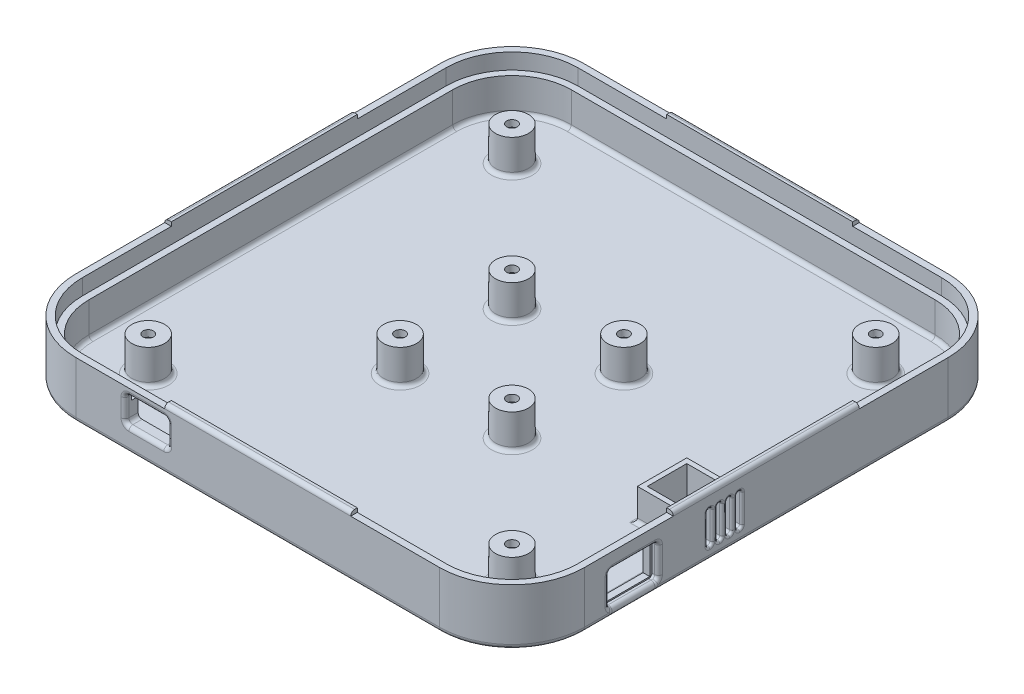
SolidWorks part; units mm, degrees
ref_plane "Front Plane" through (0, 0, 0) normal (0, 0, 1) x (1, 0, 0)
ref_plane "Top Plane" through (0, 0, 0) normal (0, 1, 0) x (1, 0, 0)
ref_plane "Right Plane" through (0, 0, 0) normal (1, 0, 0) x (0, 0, -1)
sketch "Sketch1" plane through (0, 0, 0) normal (0, 1, 0) x (1, 0, 0)
  line L0 (0, 75.25) -> (55.25, 75.25)
  line L1 (75.25, 55.25) -> (75.25, 0)
  line L2 (75.25, 0) -> (75.25, -55.25)
  line L3 (55.25, -75.25) -> (0, -75.25)
  line L4 (0, -75.25) -> (-55.25, -75.25)
  line L5 (-75.25, -55.25) -> (-75.25, 0)
  line L6 (-75.25, 0) -> (-75.25, 55.25)
  line L7 (-55.25, 75.25) -> (0, 75.25)
  line L8 (-55.25, 77.25) -> (0, 77.25)
  line L9 (0, 77.25) -> (55.25, 77.25)
  line L10 (77.25, 55.25) -> (77.25, 0)
  line L11 (77.25, 0) -> (77.25, -55.25)
  line L12 (55.25, -77.25) -> (0, -77.25)
  line L13 (0, -77.25) -> (-55.25, -77.25)
  line L14 (-77.25, -55.25) -> (-77.25, 0)
  line L15 (-77.25, 0) -> (-77.25, 55.25)
  arc A0 (55.25, 75.25) -> (75.25, 55.25) centre (55.25, 55.25) cw
  arc A1 (75.25, -55.25) -> (55.25, -75.25) centre (55.25, -55.25) cw
  arc A2 (-55.25, -75.25) -> (-75.25, -55.25) centre (-55.25, -55.25) cw
  arc A3 (-75.25, 55.25) -> (-55.25, 75.25) centre (-55.25, 55.25) cw
  arc A4 (55.25, 77.25) -> (77.25, 55.25) centre (55.25, 55.25) cw
  arc A5 (77.25, -55.25) -> (55.25, -77.25) centre (55.25, -55.25) cw
  arc A6 (-55.25, -77.25) -> (-77.25, -55.25) centre (-55.25, -55.25) cw
  arc A7 (-77.25, 55.25) -> (-55.25, 77.25) centre (-55.25, 55.25) cw
  point P24 (0, 0)
  dimension "D1" = 75.25
  dimension "D2" = 75.25
  dimension "D3" = 20
  dimension "D5" = 2
  dimension "D4" = 4
extrude "Boss-Extrude2" add sketch "Sketch1" along normal blind 15.2
sketch "Sketch4" plane through (0, 0, 0) normal (0, 1, 0) x (1, 0, 0)
  line L20 (55.25, 73.25) -> (-55.25, 73.25)
  line L21 (73.25, -55.25) -> (73.25, 55.25)
  line L22 (-55.25, -73.25) -> (55.25, -73.25)
  line L23 (-73.25, 55.25) -> (-73.25, -55.25)
  line L24 (55.25, 73.25) -> (-55.25, 73.25)
  line L25 (73.25, -55.25) -> (73.25, 55.25)
  line L26 (-55.25, -73.25) -> (55.25, -73.25)
  line L27 (-73.25, 55.25) -> (-73.25, -55.25)
  line L44 (55.25, 75.25) -> (-55.25, 75.25)
  line L45 (75.25, -55.25) -> (75.25, 55.25)
  line L46 (-55.25, -75.25) -> (55.25, -75.25)
  line L47 (-75.25, 55.25) -> (-75.25, -55.25)
  line L48 (55.25, 75.25) -> (-55.25, 75.25)
  line L49 (75.25, -55.25) -> (75.25, 55.25)
  line L50 (-55.25, -75.25) -> (55.25, -75.25)
  line L51 (-75.25, 55.25) -> (-75.25, -55.25)
  arc A24 (73.25, 55.25) -> (55.25, 73.25) centre (55.25, 55.25) ccw
  arc A25 (55.25, -73.25) -> (73.25, -55.25) centre (55.25, -55.25) ccw
  arc A26 (-73.25, -55.25) -> (-55.25, -73.25) centre (-55.25, -55.25) ccw
  arc A27 (-55.25, 73.25) -> (-73.25, 55.25) centre (-55.25, 55.25) ccw
  arc A28 (73.25, 55.25) -> (55.25, 73.25) centre (55.25, 55.25) ccw
  arc A29 (55.25, -73.25) -> (73.25, -55.25) centre (55.25, -55.25) ccw
  arc A30 (-73.25, -55.25) -> (-55.25, -73.25) centre (-55.25, -55.25) ccw
  arc A31 (-55.25, 73.25) -> (-73.25, 55.25) centre (-55.25, 55.25) ccw
  arc A52 (75.25, 55.25) -> (55.25, 75.25) centre (55.25, 55.25) ccw
  arc A53 (55.25, -75.25) -> (75.25, -55.25) centre (55.25, -55.25) ccw
  arc A54 (-75.25, -55.25) -> (-55.25, -75.25) centre (-55.25, -55.25) ccw
  arc A55 (-55.25, 75.25) -> (-75.25, 55.25) centre (-55.25, 55.25) ccw
  arc A56 (75.25, 55.25) -> (55.25, 75.25) centre (55.25, 55.25) ccw
  arc A57 (55.25, -75.25) -> (75.25, -55.25) centre (55.25, -55.25) ccw
  arc A58 (-75.25, -55.25) -> (-55.25, -75.25) centre (-55.25, -55.25) ccw
  arc A59 (-55.25, 75.25) -> (-75.25, 55.25) centre (-55.25, 55.25) ccw
  dimension "D1" = 2
  dimension "D2" = 0
extrude "Boss-Extrude3" add sketch "Sketch4" along normal blind 10.4
sketch "Sketch5" plane through (0, 0, 0) normal (0, -1, 0) x (1, 0, 0)
  line L8 (-55.25, -77.25) -> (55.25, -77.25)
  line L9 (77.25, -55.25) -> (77.25, 55.25)
  line L10 (55.25, 77.25) -> (-55.25, 77.25)
  line L11 (-77.25, 55.25) -> (-77.25, -55.25)
  line L12 (-55.25, -77.25) -> (55.25, -77.25)
  line L13 (77.25, -55.25) -> (77.25, 55.25)
  line L14 (55.25, 77.25) -> (-55.25, 77.25)
  line L15 (-77.25, 55.25) -> (-77.25, -55.25)
  arc A8 (-77.25, -55.25) -> (-55.25, -77.25) centre (-55.25, -55.25) ccw
  arc A9 (55.25, -77.25) -> (77.25, -55.25) centre (55.25, -55.25) ccw
  arc A10 (77.25, 55.25) -> (55.25, 77.25) centre (55.25, 55.25) ccw
  arc A11 (-55.25, 77.25) -> (-77.25, 55.25) centre (-55.25, 55.25) ccw
  arc A12 (-77.25, -55.25) -> (-55.25, -77.25) centre (-55.25, -55.25) ccw
  arc A13 (55.25, -77.25) -> (77.25, -55.25) centre (55.25, -55.25) ccw
  arc A14 (77.25, 55.25) -> (55.25, 77.25) centre (55.25, 55.25) ccw
  arc A15 (-55.25, 77.25) -> (-77.25, 55.25) centre (-55.25, 55.25) ccw
  dimension "D1" = 0
extrude "Boss-Extrude4" add sketch "Sketch5" along normal blind 2
sketch "Sketch6" plane through (0, 0, 77.25) normal (0, 0, 1) x (1, 0, 0)
  line L0 (-77.25, 15.2) -> (-77.25, -2) construction
  line L1 (-40.325, 5) -> (-27.325, 5)
  line L2 (-40.325, 5) -> (-40.325, 13)
  line L3 (-40.325, 13) -> (-27.325, 13)
  line L4 (-27.325, 5) -> (-27.325, 13)
  line L5 (-40.325, 5) -> (-27.325, 13) construction
  line L6 (-40.325, 13) -> (-27.325, 5) construction
  line L7 (55.25, -2) -> (-55.25, -2) construction
  point P0 (-33.825, 9)
  dimension "D1" = 13
  dimension "D2" = 43.425
  dimension "D3" = 11
  dimension "D4" = 8
extrude "Cut-Extrude1" cut sketch "Sketch6" against normal up to next
sketch "Sketch7" plane through (77.25, 0, 0) normal (1, 0, 0) x (0, 0, -1)
  line L0 (-13.4, 11.6) -> (-13.4, 1.6)
  line L1 (-17.9, 11.6) -> (-16.4, 11.6)
  line L2 (-17.9, 11.6) -> (-17.9, 1.6)
  line L3 (-17.9, 1.6) -> (-16.4, 1.6)
  line L4 (-16.4, 11.6) -> (-16.4, 1.6)
  line L5 (-14.9, 11.6) -> (-13.4, 11.6)
  line L6 (-14.9, 11.6) -> (-14.9, 1.6)
  line L7 (-14.9, 1.6) -> (-13.4, 1.6)
  line L8 (-10.4, 11.6) -> (-10.4, 1.6)
  line L9 (-11.9, 11.6) -> (-10.4, 11.6)
  line L10 (-11.9, 11.6) -> (-11.9, 1.6)
  line L11 (-11.9, 1.6) -> (-10.4, 1.6)
  line L12 (-7.4, 11.6) -> (-7.4, 1.6)
  line L13 (-8.9, 11.6) -> (-7.4, 11.6)
  line L14 (-8.9, 11.6) -> (-8.9, 1.6)
  line L15 (-8.9, 1.6) -> (-7.4, 1.6)
  line L16 (-13.4, 6.6) -> (-11.9, 6.6) construction
  line L17 (-14.9, 6.6) -> (-16.4, 6.6) construction
  line L18 (-10.4, 6.6) -> (-8.9, 6.6) construction
  line L19 (-77.25, 15.2) -> (-77.25, -2) construction
  line L21 (-55.25, 6.6) -> (55.25, 6.6) construction
  line L22 (-55.25, 15.2) -> (-55.25, -2) construction
  line L23 (55.25, 15.2) -> (55.25, -2) construction
  point P22 (-12.65, 6.6)
  dimension "D1" = 1.5
  dimension "D3" = 64.6
  dimension "D4" = 1.5
  dimension "D5" = 10
  dimension "D2" = 4
extrude "Cut-Extrude2" cut sketch "Sketch7" against normal up to next
fillet "Fillet4" radius 1.5 8 edges at (70.8063, -2, 70.8063) (77.25, -2, 0) (70.8063, -2, -70.8063) (0, -2, -77.25) (-70.8063, -2, -70.8063) (-77.25, -2, 0) (-70.8063, -2, 70.8063) (0, -2, 77.25)
sketch "Sketch10" plane through (0, 0, 0) normal (0, 1, 0) x (1, 0, 0)
  line L0 (73.25, -55.25) -> (73.25, 55.25) construction
  line L1 (73.25, -5.15) -> (58.25, -5.15)
  line L2 (73.25, -5.15) -> (73.25, -6.65)
  line L3 (73.25, -20.15) -> (58.25, -20.15)
  line L4 (58.25, -5.15) -> (58.25, -20.15)
  line L5 (-55.25, -77.25) -> (55.25, -77.25) construction
  line L6 (73.25, -18.65) -> (73.25, -20.15)
  line L7 (73.25, -6.65) -> (59.75, -6.65)
  line L9 (73.25, -18.65) -> (59.75, -18.65)
  line L10 (59.75, -6.65) -> (59.75, -18.65)
  point P7 (58.25, -12.65)
  dimension "D1" = 15
  dimension "D2" = 15
  dimension "D3" = 64.6
  dimension "D4" = 1.5
  dimension "D5" = 1.5
  dimension "D6" = 1.5
extrude "Boss-Extrude6" add sketch "Sketch10" along normal blind 9.5
sketch "Sketch14" plane through (0, -2, 0) normal (0, -1, 0) x (1, 0, 0)
  line L0 (-77.25, -55.25) -> (-77.25, 55.25) construction
  line L1 (-55.25, 77.25) -> (55.25, 77.25) construction
  line L2 (-75.75, 0) -> (75.75, 0) construction
  line L3 (-75.75, 55.25) -> (-75.75, -55.25) construction
  line L4 (75.75, -55.25) -> (75.75, 55.25) construction
  circle A0 centre (-55.25, 55.25) radius 3
  circle A1 centre (-17, 17) radius 3
  dimension "D1" = 6
  dimension "D4" = 6
  dimension "D2" = 22
  dimension "D3" = 22
  dimension "D5" = 17
  dimension "D6" = 17
extrude "Cut-Extrude5" cut sketch "Sketch14" against normal offset from surface (10.4 mm away) 2 up to face at (-12.4388, 10.4, -6.4731)
sketch "Sketch15" plane through (0, 0, 0) normal (0, 1, 0) x (1, 0, 0)
  circle A0 centre (-55.25, -55.25) radius 3
  circle A1 centre (-55.25, -55.25) radius 5
  circle A2 centre (-17, -17) radius 3
  circle A3 centre (-17, -17) radius 5
  dimension "D1" = 2
  dimension "D2" = 2
extrude "Boss-Extrude8" add sketch "Sketch15" along normal offset from surface (8.4 mm away) 2 up to face at (-12.4388, 10.4, -6.4731)
sketch "Sketch16" plane through (0, 8.4, 0) normal (0, 1, 0) x (1, 0, 0)
  circle A0 centre (-55.25, -55.25) radius 5
  circle A1 centre (-55.25, -55.25) radius 1.6
  circle A3 centre (-17, -17) radius 1.6
  circle A4 centre (-17, -17) radius 5
  dimension "D1" = 3.2
  dimension "D2" = 3.2
extrude "Boss-Extrude9" add sketch "Sketch16" along normal up to surface (2 mm away) up to face at (-12.4388, 10.4, -6.4731)
mirror "Mirror1" about plane through (0, 0, 0) normal (0, 0, 1) of "Boss-Extrude8", "Boss-Extrude9", "Cut-Extrude5"
mirror "Mirror2" about plane through (0, 0, 0) normal (1, 0, 0) of "Mirror1"
sketch "Sketch17" plane through (0, 15.2, 0) normal (0, 1, 0) x (1, 0, 0)
  line L0 (-55.25, -75.25) -> (55.25, -75.25) construction
  line L1 (-28.25, -75.25) -> (28.25, -75.25)
  line L2 (-28.25, -75.25) -> (-28.25, -77.25)
  line L3 (-28.25, -77.25) -> (28.25, -77.25)
  line L4 (28.25, -75.25) -> (28.25, -77.25)
  line L5 (-55.25, -77.25) -> (55.25, -77.25) construction
  line L6 (77.25, -55.25) -> (77.25, 55.25) construction
  line L7 (77.25, 28.25) -> (75.25, 28.25)
  line L8 (77.25, 28.25) -> (77.25, -28.25)
  line L9 (77.25, -28.25) -> (75.25, -28.25)
  line L10 (75.25, 28.25) -> (75.25, -28.25)
  line L11 (75.25, -55.25) -> (75.25, 55.25) construction
  line L12 (55.25, 77.25) -> (-55.25, 77.25) construction
  line L13 (28.25, 77.25) -> (-28.25, 77.25)
  line L14 (28.25, 77.25) -> (28.25, 75.25)
  line L15 (28.25, 75.25) -> (-28.25, 75.25)
  line L16 (-28.25, 77.25) -> (-28.25, 75.25)
  line L17 (55.25, 75.25) -> (-55.25, 75.25) construction
  line L18 (-75.25, 55.25) -> (-75.25, -55.25) construction
  line L19 (-75.25, 28.25) -> (-77.25, 28.25)
  line L20 (-75.25, 28.25) -> (-75.25, -28.25)
  line L21 (-75.25, -28.25) -> (-77.25, -28.25)
  line L22 (-77.25, 28.25) -> (-77.25, -28.25)
  line L23 (-77.25, 55.25) -> (-77.25, -55.25) construction
  dimension "D1" = 27
  dimension "D2" = 27
  dimension "D3" = 27
  dimension "D4" = 27
  dimension "D5" = 27
  dimension "D6" = 27
  dimension "D7" = 27
  dimension "D8" = 27
extrude "Boss-Extrude10" add sketch "Sketch17" along normal blind 1.2
fillet "Fillet7" radius 1.2 4 edges at (0, 16.4, 77.25) (77.25, 16.4, 0) (0, 16.4, -77.25) (-77.25, 16.4, 0)
fillet "Fillet8" radius 1.2 8 edges at (-40.325, 9, 77.25) (-33.825, 5, 77.25) (-33.825, 13, 77.25) (-27.325, 9, 77.25) (-27.325, 13, 76.25) (-40.325, 13, 76.25) (-40.325, 5, 75.25) (-27.325, 5, 75.25)
fillet "Fillet9" radius 0.75 40 edges at (75.25, 11, 7.4) (75.25, 11, 8.9) (75.25, 11, 10.4) (75.25, 11, 11.9) (75.25, 11, 13.4) (75.25, 11, 14.9) (75.25, 11, 16.4) (75.25, 11, 17.9) (73.25, 6, 8.9) (73.25, 6, 7.4) (73.25, 6, 11.9) (73.25, 6, 10.4) (73.25, 6, 14.9) (73.25, 6, 13.4) (73.25, 6, 17.9) (73.25, 6, 16.4) (77.25, 6.6, 17.9) (76.25, 11.6, 8.9) (76.25, 11.6, 7.4) (76.25, 11.6, 11.9) (76.25, 11.6, 10.4) (76.25, 11.6, 14.9) (76.25, 11.6, 13.4) (76.25, 11.6, 17.9) (76.25, 11.6, 16.4) (75.25, 1.6, 7.4) (75.25, 1.6, 8.9) (75.25, 1.6, 10.4) (75.25, 1.6, 11.9) (75.25, 1.6, 13.4) (75.25, 1.6, 14.9) (75.25, 1.6, 16.4) (75.25, 1.6, 17.9) (77.25, 6.6, 8.9) (77.25, 6.6, 11.9) (77.25, 6.6, 14.9) (77.25, 6.6, 10.4) (77.25, 6.6, 13.4) (77.25, 6.6, 16.4) (77.25, 6.6, 7.4)
fillet "Fillet10" radius 1.2 20 edges at (17, 0, -22) (-17, 0, 12) (58.25, 0, 12.65) (65.75, 0, 20.15) (73.25, 0, 37.7) (67.9779, 0, 67.9779) (0, 0, 73.25) (-67.9779, 0, 67.9779) (-73.25, 0, 0) (-67.9779, 0, -67.9779) (0, 0, -73.25) (67.9779, 0, -67.9779) (73.25, 0, -25.05) (65.75, 0, 5.15) (-55.25, 0, 50.25) (-55.25, 0, -60.25) (-17, 0, -22) (55.25, 0, -60.25) (55.25, 0, 60.25) (17, 0, 22)
sketch "Sketch18" plane through (77.25, 0, 0) normal (1, 0, 0) x (0, 0, -1)
  line L0 (55.25, -2) -> (-55.25, -2) construction
  line L1 (-46.75, 0.5) -> (-33.75, 0.5)
  line L2 (-47.75, 1.5) -> (-47.75, 9.5)
  line L3 (-46.75, 10.5) -> (-33.75, 10.5)
  line L4 (-32.75, 1.5) -> (-32.75, 9.5)
  line L5 (-47.75, 0.5) -> (-32.75, 10.5) construction
  line L6 (-47.75, 10.5) -> (-32.75, 0.5) construction
  arc A0 (-33.75, 10.5) -> (-32.75, 9.5) centre (-33.75, 9.5) cw
  arc A1 (-33.75, 0.5) -> (-32.75, 1.5) centre (-33.75, 1.5) ccw
  arc A2 (-46.75, 0.5) -> (-47.75, 1.5) centre (-46.75, 1.5) cw
  arc A3 (-47.75, 9.5) -> (-46.75, 10.5) centre (-46.75, 9.5) cw
  point P0 (-40.25, 5.5)
  dimension "D3" = 1
  dimension "D1" = 15
  dimension "D2" = 10
  dimension "D4" = 7.5
  dimension "D5" = 37
extrude "Cut-Extrude6" cut sketch "Sketch18" against normal blind 2
sketch "Sketch19" plane through (75.25, 0, 0) normal (1, 0, 0) x (0, 0, -1)
  line L0 (55.25, -2) -> (-55.25, -2) construction
  line L1 (-47.1, 0.9) -> (-33.4, 0.9)
  line L2 (-47.1, 0.9) -> (-47.1, 10.1)
  line L3 (-47.1, 10.1) -> (-33.4, 10.1)
  line L4 (-33.4, 0.9) -> (-33.4, 10.1)
  line L5 (-47.1, 0.9) -> (-33.4, 10.1) construction
  line L6 (-47.1, 10.1) -> (-33.4, 0.9) construction
  line L7 (-77.25, 15.2) -> (-77.25, -0.5) construction
  point P0 (-40.25, 5.5)
  dimension "D1" = 13.7
  dimension "D2" = 9.2
  dimension "D3" = 7.5
  dimension "D4" = 37
extrude "Cut-Extrude7" cut sketch "Sketch19" against normal up to next
fillet "Fillet11" radius 1.2 8 edges at (77.25, 0.7929, 33.0429) (77.25, 0.7929, 47.4571) (77.25, 5.5, 47.75) (77.25, 10.2071, 47.4571) (77.25, 10.5, 40.25) (77.25, 10.2071, 33.0429) (77.25, 5.5, 32.75) (77.25, 0.5, 40.25)
